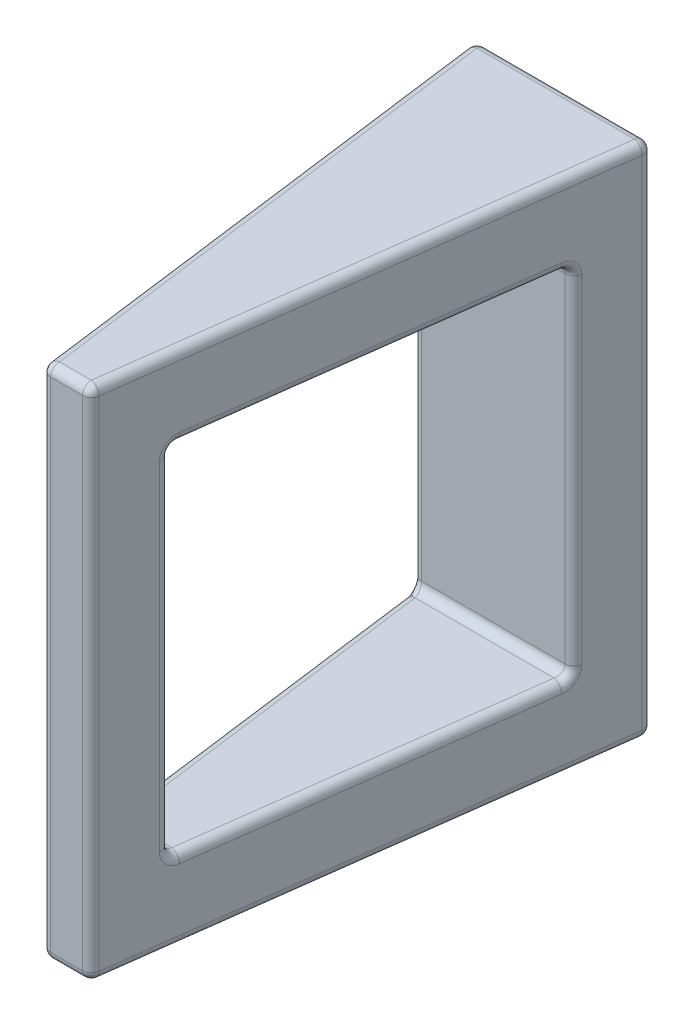
SolidWorks part; units mm, degrees
ref_plane "Front Plane" through (0, 0, 0) normal (1, 0, 0) x (0, 1, 0)
ref_plane "Top Plane" through (0, 0, 0) normal (0, 0, 1) x (0, 1, 0)
ref_plane "Right Plane" through (0, 0, 0) normal (0, 1, 0) x (-1, 0, 0)
sketch "A-Frame Profile" plane through (0, 0, 0) normal (0, 1, 0) x (-1, 0, 0)
  line L0 (-31.75, 0) -> (31.75, 0)
  line L1 (31.75, 0) -> (8.4667, 177.8)
  line L2 (8.4667, 177.8) -> (-8.4667, 177.8)
  line L3 (-8.4667, 177.8) -> (-31.75, 0)
extrude "A-Frame Body" add sketch "A-Frame Profile" along normal blind 92.075 and the other way blind 92.075
sketch "Window Sketch" plane through (0, 0, 0) normal (1, 0, 0) x (0, 1, 0)
  line L0 (-63.5, 25.4) -> (63.5, 25.4)
  line L1 (63.5, 25.4) -> (63.5, 152.4)
  line L2 (63.5, 152.4) -> (-63.5, 152.4)
  line L3 (-63.5, 152.4) -> (-63.5, 25.4)
extrude "Window Cutout" cut sketch "Window Sketch" against normal through all and the other way through all
sketch "Mounting Holes Sketch" plane through (0, 0, 0) normal (0, 0, 1) x (0, 1, 0)
  circle A0 centre (-31.75, 0) radius 3.9688
  circle A1 centre (31.75, 0) radius 3.9688
extrude "Mounting Holes" cut sketch "Mounting Holes Sketch" along normal blind 12.7
fillet "External Fillets" radius 3.175 28 edges at (3.9688, 31.75, 12.7) (3.9688, 31.75, 0) (3.9688, -31.75, 0) (3.9688, -31.75, 12.7) (0, -63.5, 25.4) (0, 63.5, 25.4) (0, 63.5, 152.4) (0, -63.5, 152.4) (28.4238, 0, 25.4) (20.1083, 63.5, 88.9) (11.7929, 0, 152.4) (20.1083, -63.5, 88.9) (20.1083, 92.075, 88.9) (0, 92.075, 0) (-20.1083, 92.075, 88.9) (0, 92.075, 177.8) (20.1083, -92.075, 88.9) (0, -92.075, 0) (-20.1083, -92.075, 88.9) (0, -92.075, 177.8) (31.75, 0, 0) (-31.75, 0, 0) (-8.4667, 0, 177.8) (8.4667, 0, 177.8) (-28.4238, 0, 25.4) (-20.1083, 63.5, 88.9) (-11.7929, 0, 152.4) (-20.1083, -63.5, 88.9) tangent propagation no
